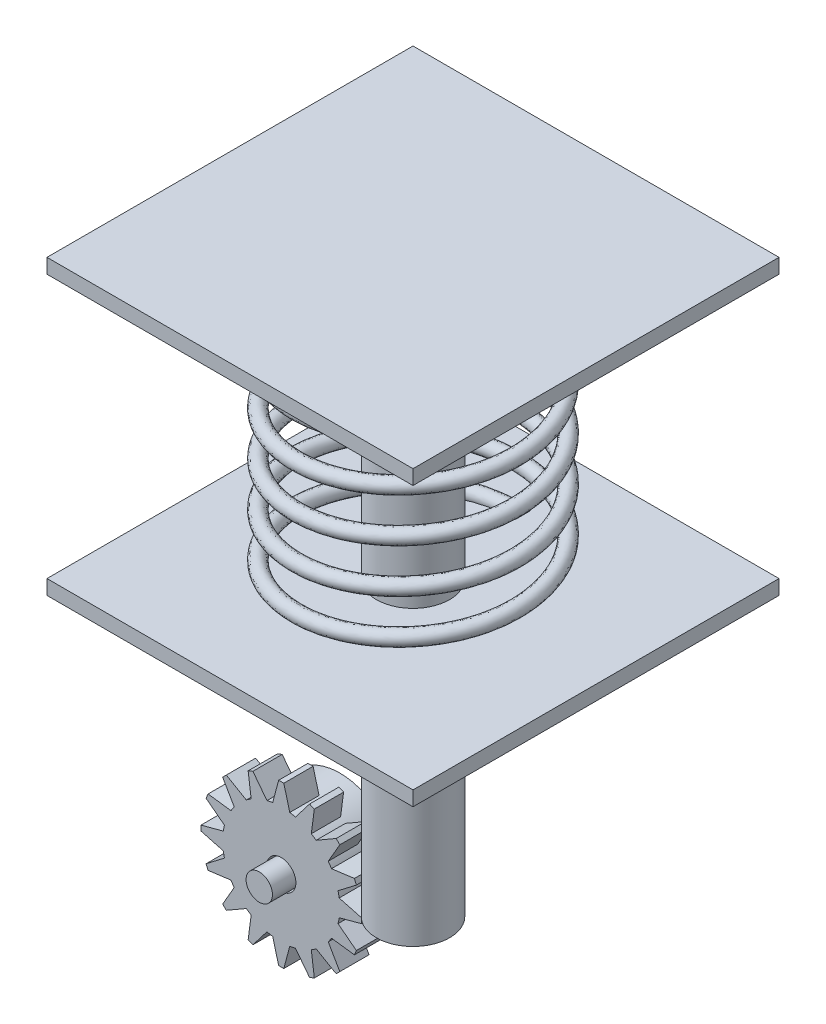
SolidWorks part; units mm, degrees
ref_plane "Front Plane" through (0, 0, 0) normal (0, 0, 1) x (1, 0, 0)
ref_plane "Top Plane" through (0, 0, 0) normal (0, 1, 0) x (1, 0, 0)
ref_plane "Right Plane" through (0, 0, 0) normal (1, 0, 0) x (0, 0, -1)
sketch "Sketch1" plane through (0, 0, 0) normal (0, 1, 0) x (1, 0, 0)
  circle A0 centre (0, 0) radius 5
extrude "Extrude1" add sketch "Sketch1" along normal blind 56 and the other way blind 20
shell "Shell1" thickness 2
sketch "Sketch2" plane through (0, 56, 0) normal (0, 1, 0) x (1, 0, 0)
  circle A0 centre (0, 0) radius 15
sketch "Sketch3" plane through (0, 56, 0) normal (0, 1, 0) x (1, 0, 0)
  circle A0 centre (0, 0) radius 15 construction
  circle A1 centre (0, 0) radius 15
curve "Helix/Spiral1" pitch 6 height 36 turns 6
sketch "Sketch4" plane through (0, 0, 0) normal (1, 0, 0) x (0, 0, -1)
  line L0 (15, 56) -> (-15, 56) construction
  circle A0 centre (15, 56) radius 1
  spline S0 degree 3 poles (15, 56) (15, 55.883) (14.3092, 55.6467) (11.3404, 55.2942) (6.84, 54.9412) (1.4159, 54.5882) (-4.1995, 54.2353) (-9.2477, 53.8824) (-13.0469, 53.5294) (-15.0841, 53.1765) (-15.0841, 52.8235) (-13.0469, 52.4706) (-9.2477, 52.1176) (-4.1995, 51.7647) (1.4159, 51.4118) (6.84, 51.0588) (11.3404, 50.7059) (14.3092, 50.3529) (15.3454, 50) (14.3092, 49.6471) (11.3404, 49.2941) (6.84, 48.9412) (1.4159, 48.5882) (-4.1995, 48.2353) (-9.2477, 47.8824) (-13.0469, 47.5294) (-15.0841, 47.1765) (-15.0841, 46.8235) (-13.0469, 46.4706) (-9.2477, 46.1176) (-4.1995, 45.7647) (1.4159, 45.4118) (6.84, 45.0588) (11.3404, 44.7059) (14.3092, 44.3529) (15.3454, 44) (14.3092, 43.6471) (11.3404, 43.2941) (6.84, 42.9412) (1.4159, 42.5882) (-4.1995, 42.2353) (-9.2477, 41.8824) (-13.0469, 41.5294) (-15.0841, 41.1765) (-15.0841, 40.8235) (-13.0469, 40.4706) (-9.2477, 40.1176) (-4.1995, 39.7647) (1.4159, 39.4118) (6.84, 39.0588) (11.3404, 38.7059) (14.3092, 38.3529) (15.3454, 38) (14.3092, 37.6471) (11.3404, 37.2941) (6.84, 36.9412) (1.4159, 36.5882) (-4.1995, 36.2353) (-9.2477, 35.8824) (-13.0469, 35.5294) (-15.0841, 35.1765) (-15.0841, 34.8235) (-13.0469, 34.4706) (-9.2477, 34.1176) (-4.1995, 33.7647) (1.4159, 33.4118) (6.84, 33.0588) (11.3404, 32.7059) (14.3092, 32.3529) (15.3454, 32) (14.3092, 31.6471) (11.3404, 31.2941) (6.84, 30.9412) (1.4159, 30.5882) (-4.1995, 30.2353) (-9.2477, 29.8824) (-13.0469, 29.5294) (-15.0841, 29.1765) (-15.0841, 28.8235) (-13.0469, 28.4706) (-9.2477, 28.1176) (-4.1995, 27.7647) (1.4159, 27.4118) (6.84, 27.0588) (11.3404, 26.7059) (14.3092, 26.3529) (15.3454, 26) (14.3092, 25.6471) (11.3404, 25.2941) (6.84, 24.9412) (1.4159, 24.5882) (-4.1995, 24.2353) (-9.2477, 23.8824) (-13.0469, 23.5294) (-15.0841, 23.1765) (-15.0841, 22.8235) (-13.0469, 22.4706) (-9.2477, 22.1176) (-4.1995, 21.7647) (1.4159, 21.4118) (6.84, 21.0588) (11.3404, 20.7058) (14.3092, 20.3533) (15, 20.117) (15, 20) knots 0 0 0 0 0.009804 0.019608 0.029412 0.039216 0.04902 0.058824 0.068627 0.078431 0.088235 0.098039 0.107843 0.117647 0.127451 0.137255 0.147059 0.156863 0.166667 0.176471 0.186275 0.196078 0.205882 0.215686 0.22549 0.235294 0.245098 0.254902 0.264706 0.27451 0.284314 0.294118 0.303922 0.313725 0.323529 0.333333 0.343137 0.352941 0.362745 0.372549 0.382353 0.392157 0.401961 0.411765 0.421569 0.431373 0.441176 0.45098 0.460784 0.470588 0.480392 0.490196 0.5 0.509804 0.519608 0.529412 0.539216 0.54902 0.558824 0.568627 0.578431 0.588235 0.598039 0.607843 0.617647 0.627451 0.637255 0.647059 0.656863 0.666667 0.676471 0.686275 0.696078 0.705882 0.715686 0.72549 0.735294 0.745098 0.754902 0.764706 0.77451 0.784314 0.794118 0.803922 0.813725 0.823529 0.833333 0.843137 0.852941 0.862745 0.872549 0.882353 0.892157 0.901961 0.911765 0.921569 0.931373 0.941176 0.95098 0.960784 0.970588 0.980392 0.990196 1 1 1 1 construction
ref_plane "Plane1" through (0, 56, 0) normal (0, 1, 0) x (-1, 0, 0)
sketch "Sketch7" plane through (0, 56, 0) normal (0, 1, 0) x (-1, 0, 0)
  line L1 (-25, 25) -> (25, 25)
  line L2 (-25, 25) -> (-25, -25)
  line L3 (-25, -25) -> (25, -25)
  line L4 (25, 25) -> (25, -25)
extrude "Extrude4" add sketch "Sketch7" along normal blind 2 contours L4 L3 L2 L1
sketch "Sketch9" plane through (0, 0, 0) normal (0, 0, 1) x (1, 0, 0)
  circle A0 centre (14.9883, 30.4633) radius 1
  spline S0 degree 3 poles (0, 56) (1.8375, 55.883) (5.5482, 55.6467) (10.3369, 55.2942) (13.737, 54.9412) (15.2799, 54.5882) (14.7596, 54.2353) (12.2459, 53.8824) (8.0783, 53.5294) (2.8197, 53.1765) (-2.8197, 52.8235) (-8.0783, 52.4706) (-12.2459, 52.1176) (-14.7596, 51.7647) (-15.28, 51.4118) (-13.7367, 51.0588) (-10.3381, 50.7059) (-5.5434, 50.3529) (0, 50) (5.5434, 49.6471) (10.3381, 49.2941) (13.7367, 48.9412) (15.28, 48.5882) (14.7596, 48.2353) (12.2459, 47.8824) (8.0783, 47.5294) (2.8197, 47.1765) (-2.8197, 46.8235) (-8.0783, 46.4706) (-12.2459, 46.1176) (-14.7596, 45.7647) (-15.28, 45.4118) (-13.7367, 45.0588) (-10.3381, 44.7059) (-5.5434, 44.3529) (0, 44) (5.5434, 43.6471) (10.3381, 43.2941) (13.7367, 42.9412) (15.28, 42.5882) (14.7596, 42.2353) (12.2459, 41.8824) (8.0783, 41.5294) (2.8197, 41.1765) (-2.8197, 40.8235) (-8.0783, 40.4706) (-12.2459, 40.1176) (-14.7596, 39.7647) (-15.28, 39.4118) (-13.7367, 39.0588) (-10.3381, 38.7059) (-5.5434, 38.3529) (0, 38) (5.5434, 37.6471) (10.3381, 37.2941) (13.7367, 36.9412) (15.28, 36.5882) (14.7596, 36.2353) (12.2459, 35.8824) (8.0783, 35.5294) (2.8197, 35.1765) (-2.8197, 34.8235) (-8.0783, 34.4706) (-12.2459, 34.1176) (-14.7596, 33.7647) (-15.28, 33.4118) (-13.7367, 33.0588) (-10.3381, 32.7059) (-5.5434, 32.3529) (0, 32) (5.5434, 31.6471) (10.3381, 31.2941) (13.7367, 30.9412) (15.28, 30.5882) (14.7596, 30.2353) (12.2459, 29.8824) (8.0783, 29.5294) (2.8197, 29.1765) (-2.8197, 28.8235) (-8.0783, 28.4706) (-12.2459, 28.1176) (-14.7596, 27.7647) (-15.28, 27.4118) (-13.7367, 27.0588) (-10.3381, 26.7059) (-5.5434, 26.3529) (0, 26) (5.5434, 25.6471) (10.3381, 25.2941) (13.7367, 24.9412) (15.28, 24.5882) (14.7596, 24.2353) (12.2459, 23.8824) (8.0783, 23.5294) (2.8197, 23.1765) (-2.8197, 22.8235) (-8.0783, 22.4706) (-12.2459, 22.1176) (-14.7596, 21.7647) (-15.2799, 21.4118) (-13.737, 21.0588) (-10.3369, 20.7058) (-5.5482, 20.3533) (-1.8375, 20.117) (0, 20) knots 0 0 0 0 0.009804 0.019608 0.029412 0.039216 0.04902 0.058824 0.068627 0.078431 0.088235 0.098039 0.107843 0.117647 0.127451 0.137255 0.147059 0.156863 0.166667 0.176471 0.186275 0.196078 0.205882 0.215686 0.22549 0.235294 0.245098 0.254902 0.264706 0.27451 0.284314 0.294118 0.303922 0.313725 0.323529 0.333333 0.343137 0.352941 0.362745 0.372549 0.382353 0.392157 0.401961 0.411765 0.421569 0.431373 0.441176 0.45098 0.460784 0.470588 0.480392 0.490196 0.5 0.509804 0.519608 0.529412 0.539216 0.54902 0.558824 0.568627 0.578431 0.588235 0.598039 0.607843 0.617647 0.627451 0.637255 0.647059 0.656863 0.666667 0.676471 0.686275 0.696078 0.705882 0.715686 0.72549 0.735294 0.745098 0.754902 0.764706 0.77451 0.784314 0.794118 0.803922 0.813725 0.823529 0.833333 0.843137 0.852941 0.862745 0.872549 0.882353 0.892157 0.901961 0.911765 0.921569 0.931373 0.941176 0.95098 0.960784 0.970588 0.980392 0.990196 1 1 1 1 construction
sweep "Sweep2" add profiles "Sketch9" path "Helix/Spiral1"
ref_plane "Plane2" through (0, 20, 0) normal (0, 1, 0) x (-1, 0, 0)
sketch "Sketch10" plane through (0, 20, 0) normal (0, 1, 0) x (-1, 0, 0)
  line L1 (25, 25) -> (-25, 25)
  line L2 (25, 25) -> (25, -25)
  line L3 (25, -25) -> (-25, -25)
  line L4 (-25, 25) -> (-25, -25)
sketch "Sketch11" plane through (0, 20, 0) normal (0, 1, 0) x (-1, 0, 0)
  circle A0 centre (0, 0) radius 7
extrude "Extrude5" add sketch "Sketch10" along normal blind 0.0001 and the other way blind 2 contours L2 L3 L4 L1
sketch "Sketch14" plane through (0, 0, 0) normal (0, 0, 1) x (1, 0, 0)
  line L0 (-25, 18) -> (-25, -30.6542) construction
  line L1 (-16, -22) -> (-16, -8.2507) construction
  circle A1 centre (-16, -22) radius 8
extrude "Extrude9" add sketch "Sketch14" along normal blind 2 and the other way blind 6
sketch "Sketch19" plane through (0, 0, -6) normal (0, 0, -1) x (-1, 0, 0)
  circle A0 centre (16, -22) radius 2
extrude "Cut-Extrude2" cut sketch "Sketch19" against normal through all
sketch "Sketch20" plane through (0, 0, 2) normal (0, 0, 1) x (1, 0, 0)
  line L0 (-16, -22) -> (-16, -9.4271) construction
  line L1 (-17.4, -14.9491) -> (-14.6, -14.9491)
  line L2 (-14.6, -14.9491) -> (-15.6486, -11.0358)
  line L3 (-15.6486, -11.0358) -> (-16.3514, -11.0358)
  line L4 (-16.3514, -11.0358) -> (-17.4, -14.9491)
  dimension "D2" = 2.8
  dimension "D3" = 1.4
  dimension "D5" = 75
  dimension "D6" = 75
extrude "Extrude10" add sketch "Sketch20" against normal blind 4
pattern_circular "CirPattern1" count 16 over 360 about axis through (-16, -22, 0) along (0, 0, 1) of "Extrude10"
sketch "Sketch21" plane through (0, 0, 0) normal (0, 0, 1) x (1, 0, 0)
  circle A0 centre (-16, -22) radius 1.8
extrude "Extrude11" add sketch "Sketch21" along normal blind 5 and the other way blind 10
